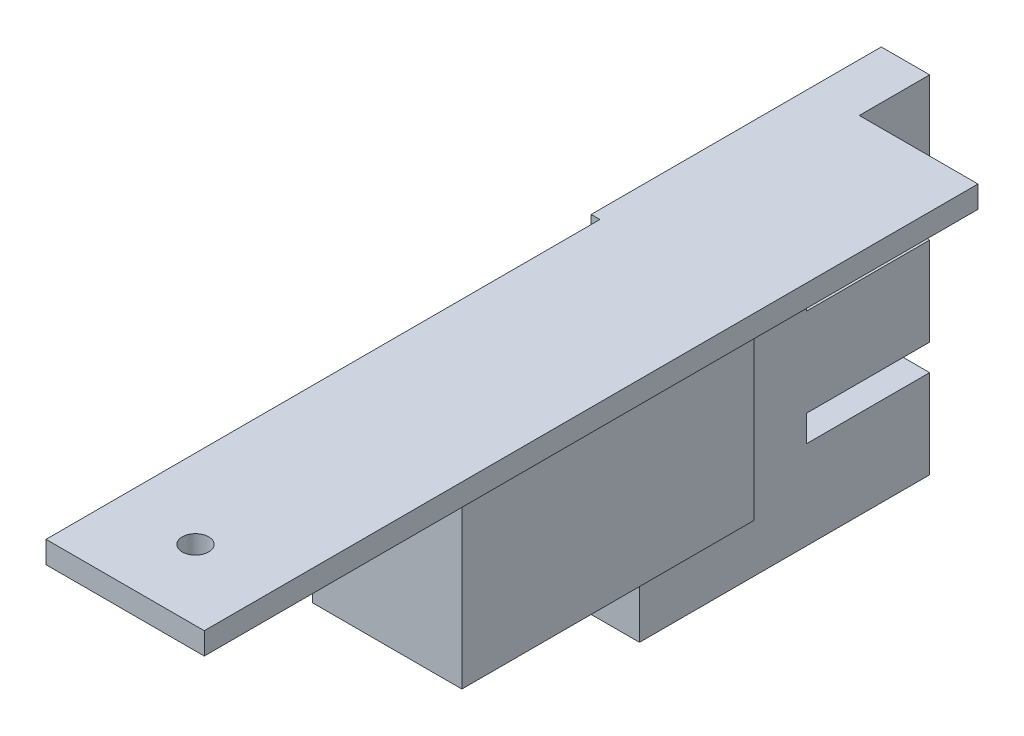
SolidWorks part; units mm, degrees
ref_plane "Front Plane" through (0, 0, 0) normal (0, 0, 1) x (1, 0, 0)
ref_plane "Top Plane" through (0, 0, 0) normal (0, 1, 0) x (1, 0, 0)
ref_plane "Right Plane" through (0, 0, 0) normal (1, 0, 0) x (0, 0, -1)
ref_plane "PZ_m80_000" through (0, 0, -80) normal (0, 0, 1) x (1, 0, 0)
sketch "S_box1" plane through (0, 0, -80) normal (0, 0, 1) x (1, 0, 0)
  line L0 (-9, 18.2) -> (9, 18.2)
  line L1 (9, 18.2) -> (9, 20.7)
  line L2 (9, 20.7) -> (-9, 20.7)
  line L3 (-9, 20.7) -> (-9, 18.2)
  dimension "P1" = 9
  dimension "P2" = 18.2
  dimension "P3" = 9
  dimension "P4" = 18.2
  dimension "P5" = 9
  dimension "P6" = 20.7
  dimension "P7" = 9
  dimension "P8" = 20.7
extrude "Boss_1" add sketch "S_box1" along normal blind 88
ref_plane "PZ_m55_000" through (0, 0, -55) normal (0, 0, 1) x (1, 0, 0)
sketch "S_box2" plane through (0, 0, -55) normal (0, 0, 1) x (1, 0, 0)
  line L0 (-8.5, -0.2) -> (8.5, -0.2)
  line L1 (8.5, -0.2) -> (8.5, 18.2)
  line L2 (8.5, 18.2) -> (-8.5, 18.2)
  line L3 (-8.5, 18.2) -> (-8.5, -0.2)
  dimension "P1" = 8.5
  dimension "P2" = 0.2
  dimension "P3" = 8.5
  dimension "P4" = 0.2
  dimension "P5" = 8.5
  dimension "P6" = 18.2
  dimension "P7" = 8.5
  dimension "P8" = 18.2
extrude "Boss_2" add sketch "S_box2" along normal blind 33.2
ref_plane "PZ_m88_000" through (0, 0, -88) normal (0, 0, 1) x (1, 0, 0)
sketch "S_box3" plane through (0, 0, -88) normal (0, 0, 1) x (1, 0, 0)
  line L0 (-10, -18.7) -> (-4.5, -18.7)
  line L1 (-4.5, -18.7) -> (-4.5, 20.7)
  line L2 (-4.5, 20.7) -> (-10, 20.7)
  line L3 (-10, 20.7) -> (-10, -18.7)
  dimension "P1" = 10
  dimension "P2" = 18.7
  dimension "P3" = 4.5
  dimension "P4" = 18.7
  dimension "P5" = 4.5
  dimension "P6" = 20.7
  dimension "P7" = 10
  dimension "P8" = 20.7
extrude "Boss_3" add sketch "S_box3" along normal blind 33
ref_plane "PZ_m50_200" through (0, 0, -50.2) normal (0, 0, 1) x (1, 0, 0)
sketch "S_cut4" plane through (0, 0, -50.2) normal (0, 0, 1) x (1, 0, 0)
  line L0 (-6.5, -0.3) -> (6.5, -0.3)
  line L1 (6.5, -0.3) -> (6.5, 18.2)
  line L2 (6.5, 18.2) -> (-6.5, 18.2)
  line L3 (-6.5, 18.2) -> (-6.5, -0.3)
  dimension "P1" = 6.5
  dimension "P2" = 0.3
  dimension "P3" = 6.5
  dimension "P4" = 0.3
  dimension "P5" = 6.5
  dimension "P6" = 18.2
  dimension "P7" = 6.5
  dimension "P8" = 18.2
extrude "Pocket_4" cut sketch "S_cut4" along normal blind 23.6
ref_plane "PY_p18_100" through (0, 18.1, 0) normal (0, 1, 0) x (1, 0, 0)
sketch "S_hole5" plane through (0, 18.1, 0) normal (0, 1, 0) x (1, 0, 0)
  circle A0 centre (0, 0) radius 1.5
  dimension "D1_S_hole5" = 3
extrude "Hole_5" cut sketch "S_hole5" along normal blind 2.7
ref_plane "PY_m0_300" through (0, -0.3, 0) normal (0, 1, 0) x (1, 0, 0)
sketch "S_hole6" plane through (0, -0.3, 0) normal (0, 1, 0) x (1, 0, 0)
  circle A0 centre (0, 52.4) radius 0.8
  dimension "D1_S_hole6" = 1.6
  dimension "P2" = 52.4
extrude "Hole_6" cut sketch "S_hole6" along normal blind 6.1
sketch "S_hole7" plane through (0, -0.3, 0) normal (0, 1, 0) x (1, 0, 0)
  circle A0 centre (0, 24.4) radius 0.8
  dimension "D1_S_hole7" = 1.6
  dimension "P2" = 24.4
extrude "Hole_7" cut sketch "S_hole7" along normal blind 6.1
ref_plane "PZ_m88_100" through (0, 0, -88.1) normal (0, 0, 1) x (1, 0, 0)
sketch "S_cut8" plane through (0, 0, -88.1) normal (0, 0, 1) x (1, 0, 0)
  line L0 (-10.1, -8.63) -> (-4.4, -8.63)
  line L1 (-4.4, -8.63) -> (-4.4, -5.63)
  line L2 (-4.4, -5.63) -> (-10.1, -5.63)
  line L3 (-10.1, -5.63) -> (-10.1, -8.63)
  dimension "P1" = 10.1
  dimension "P2" = 8.63
  dimension "P3" = 4.4
  dimension "P4" = 8.63
  dimension "P5" = 4.4
  dimension "P6" = 5.63
  dimension "P7" = 10.1
  dimension "P8" = 5.63
extrude "Pocket_8" cut sketch "S_cut8" along normal blind 14.1
sketch "S_cut9" plane through (0, 0, -88.1) normal (0, 0, 1) x (1, 0, 0)
  line L0 (-10.1, 4.43) -> (-4.4, 4.43)
  line L1 (-4.4, 4.43) -> (-4.4, 7.43)
  line L2 (-4.4, 7.43) -> (-10.1, 7.43)
  line L3 (-10.1, 7.43) -> (-10.1, 4.43)
  dimension "P1" = 10.1
  dimension "P2" = 4.43
  dimension "P3" = 4.4
  dimension "P4" = 4.43
  dimension "P5" = 4.4
  dimension "P6" = 7.43
  dimension "P7" = 10.1
  dimension "P8" = 7.43
extrude "Pocket_9" cut sketch "S_cut9" along normal blind 14.1
equation "\"plate_t\" = 3"
equation "\"clearance\" = 0.4"
